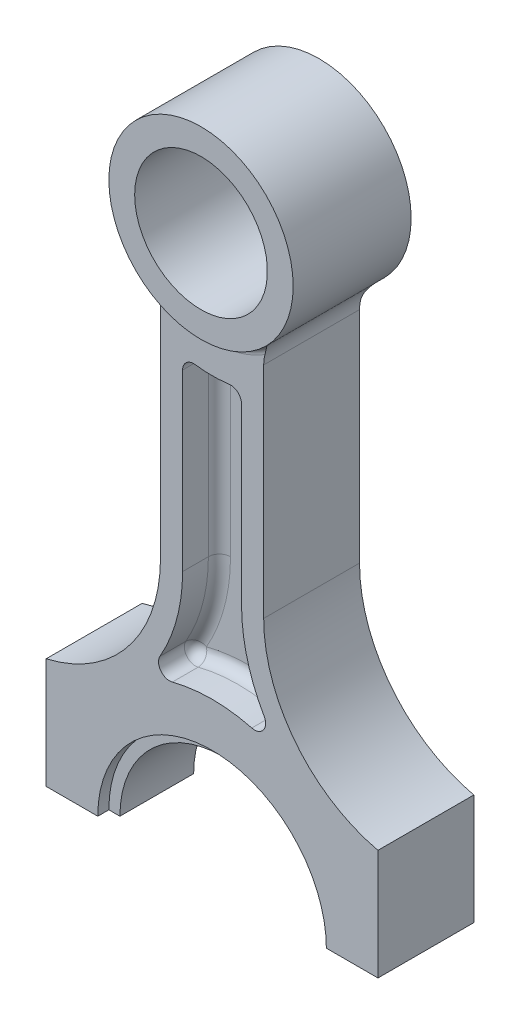
SolidWorks part; units mm, degrees
material "Простая углеродистая сталь"
ref_plane "Front" through (0, 0, 0) normal (0, 0, 1) x (1, 0, 0)
ref_plane "Top" through (0, 0, 0) normal (0, 1, 0) x (1, 0, 0)
ref_plane "Right" through (0, 0, 0) normal (1, 0, 0) x (0, 0, -1)
sketch "Эскиз1" plane through (0, 0, 0) normal (0, 0, 1) x (1, 0, 0)
  line L0 (-122.8769, 68.5524) -> (10.1507, 68.5524) construction
  line L1 (-28, 0) -> (-45, 0)
  line L2 (-45, 0) -> (-45, 30)
  line L3 (0, -61.8265) -> (0, 220.3217) construction
  line L4 (-14, 128.5245) -> (-14, 68.9744)
  line L5 (14, 128.5245) -> (14, 68.9744)
  line L6 (45, 0) -> (45, 30)
  line L7 (28, 0) -> (45, 0)
  arc A0 (28, 0) -> (-28, 0) centre (0, 0) ccw
  circle A1 centre (0, 154) radius 18
  arc A2 (17.1429, 135.8032) -> (-17.1429, 135.8032) centre (0, 154) ccw
  arc A3 (-14, 68.9744) -> (-45, 30) centre (-54, 68.9744) cw
  arc A4 (14, 68.9744) -> (45, 30) centre (54, 68.9744) ccw
  arc A5 (14, 128.5245) -> (17.1429, 135.8032) centre (24, 128.5245) cw
  arc A6 (-14, 128.5245) -> (-17.1429, 135.8032) centre (-24, 128.5245) ccw
  point P22 (14, 133.2877)
  point P25 (-14, 133.2877)
  dimension "D1" = 50
  dimension "D2" = 36
  dimension "D7" = 40
  dimension "D8" = 28
  dimension "D9" = 10
  dimension "D3" = 154
  dimension "D4" = 28
  dimension "D5" = 30
  dimension "D6" = 90
extrude "Бобышка-Вытянуть1" add sketch "Эскиз1" along normal mid plane 26
sketch "Эскиз2" plane through (0, 0, 0) normal (0, 0, 1) x (1, 0, 0)
  circle A0 centre (0, 154) radius 18 construction
  circle A1 centre (0, 154) radius 18
  arc A2 (17.1429, 135.8032) -> (-17.1429, 135.8032) centre (0, 154) ccw construction
  circle A3 centre (0, 154) radius 25
extrude "Бобышка-Вытянуть2" add sketch "Эскиз2" along normal mid plane 32
fillet "Скругление1" radius 2 2 edges at (0, 129, -13) (0, 129, 13)
sketch "Эскиз3" plane through (0, 0, 13) normal (0, 0, 1) x (1, 0, 0)
  circle A0 centre (0, 0) radius 31
  dimension "D1" = 31
extrude "Вырез-Вытянуть1" cut sketch "Эскиз3" against normal blind 3
sketch "Эскиз6" plane through (0, 0, 13) normal (0, 0, 1) x (1, 0, 0)
  line L0 (14, 68.9744) -> (14, 128.5245) construction
  line L3 (8, 68.9744) -> (8, 116.3304)
  line L5 (-8, 128.5245) -> (-8, 68.9744)
  line L6 (-8, 116.3304) -> (-8, 68.9744)
  arc A0 (14, 68.9744) -> (45, 30) centre (54, 68.9744) ccw construction
  arc A1 (31, 0) -> (-31, 0) centre (0, 0) ccw construction
  circle A2 centre (0, 154) radius 18 construction
  arc A3 (8, 68.9744) -> (14.1322, 46.0275) centre (54, 68.9744) ccw
  arc A5 (-43.65, 24.1538) -> (-8, 68.9744) centre (-54, 68.9744) ccw
  arc A6 (-14.1322, 46.0275) -> (-8, 68.9744) centre (-54, 68.9744) ccw
  arc A9 (10.78, 41.6268) -> (-10.78, 41.6268) centre (0, 0) ccw
  arc A10 (-4.6053, 119.3043) -> (-8, 116.3304) centre (-5, 116.3304) ccw
  arc A12 (-4.6053, 119.3043) -> (4.6053, 119.3043) centre (0, 154) ccw
  arc A13 (4.6053, 119.3043) -> (8, 116.3304) centre (5, 116.3304) cw
  arc A14 (14.1322, 46.0275) -> (10.78, 41.6268) centre (11.5321, 44.531) cw
  arc A15 (-10.78, 41.6268) -> (-14.1322, 46.0275) centre (-11.5321, 44.531) cw
  dimension "D5" = 3
  dimension "D6" = 3
  dimension "D3" = 43
  dimension "D4" = 35
  dimension "D1" = 6
  dimension "D2" = 6
extrude "Вырез-Вытянуть2" cut sketch "Эскиз6" against normal blind 10
fillet "Скругление3" radius 3 10 edges at (-6.9768, 118.587, 3) (0, 119, 3) (6.9768, 118.587, 3) (8, 92.6524, 3) (9.5595, 57.0983, 3) (13.9186, 42.7131, 3) (0, 43, 3) (-13.9186, 42.7131, 3) (-9.5595, 57.0983, 3) (-8, 92.6524, 3)
mirror "Зеркальное отражение1" about plane through (0, 0, 0) normal (0, 0, 1) of "Вырез-Вытянуть1", "Вырез-Вытянуть2", "Скругление3"
hole_wizard "Отверстие обработанное метчиком M81" positions "Эскиз7" profile "Эскиз8" tap size "M8" standard "ISO"
sketch "Эскиз7" plane through (0, 0, 0) normal (0, -1, 0) x (-1, 0, 0)
  line L0 (0, -21.1975) -> (0, 24.2884) construction
  point P0 (37, 0)
  point P9 (-37, 0)
  dimension "D1" = 74
sketch "Эскиз8" plane through (-37, 0, 0) normal (1, 0, 0) x (0, 0, -1)
  line L0 (0, 0) -> (0, 22.0429)
  line L1 (0, 22.0429) -> (3.4, 20)
  line L2 (3.4, 20) -> (3.4, 1.6)
  line L3 (3.4, 1.6) -> (5, 0)
  line L5 (5, 0) -> (0, 0)
  line L6 (-3.4, 1.6) -> (-5, 0) construction
  line L10 (0, 22.0429) -> (-3.4, 20) construction
  line L11 (0, -6.35) -> (0, 107.95) construction
  dimension "Диаметр сверла" = 6.8
  dimension "Глубина сверла" = 20
  dimension "Диаметр передней зенковки" = 10
  dimension "Угол передней зенковки" = 90
  dimension "Угол заточки сверла" = 118
cosmetic thread "Отверстие резьбы1" parameters "D1"=16, "D2"=8
cosmetic thread "Отверстие резьбы2" parameters "D1"=16, "D2"=8
